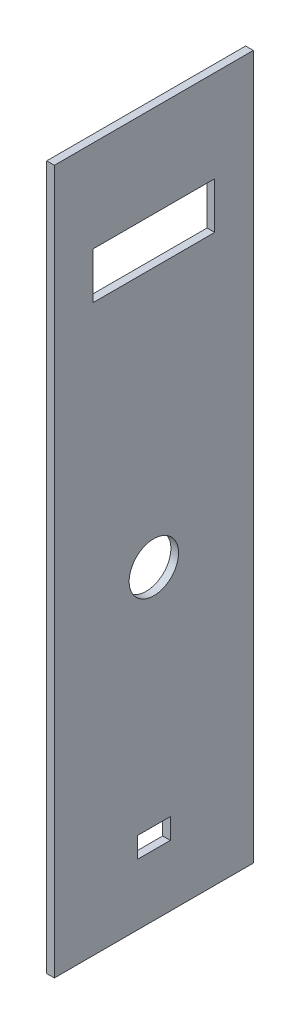
SolidWorks part; units mm, degrees
ref_plane "Front Plane" through (0, 0, 0) normal (0, 0, 1) x (1, 0, 0)
ref_plane "Top Plane" through (0, 0, 0) normal (0, 1, 0) x (1, 0, 0)
ref_plane "Right Plane" through (0, 0, 0) normal (1, 0, 0) x (0, 0, -1)
sketch "Sketch1" plane through (0, 0, 0) normal (1, 0, 0) x (0, 0, -1)
  line L1 (0, 0) -> (82.55, 0)
  line L2 (0, 0) -> (0, 292.1)
  line L3 (0, 292.1) -> (82.55, 292.1)
  line L4 (82.55, 0) -> (82.55, 292.1)
  dimension "D1" = 82.55
  dimension "D2" = 292.1
extrude "Boss-Extrude1" add sketch "Sketch1" along normal blind 3.175 contours L3 L4 L1 L2
sketch "Sketch2" plane through (0, 0, 0) normal (-1, 0, 0) x (0, 0, 1)
  line L0 (0, 292.1) -> (-82.55, 292.1) construction
  line L1 (-66.548, 234.696) -> (-16.002, 234.696)
  line L2 (-66.548, 234.696) -> (-66.548, 254)
  line L3 (-66.548, 254) -> (-16.002, 254)
  line L4 (-16.002, 234.696) -> (-16.002, 254)
  line L5 (0, 292.1) -> (-82.55, 292.1) construction
  point P8 (-41.275, 292.1)
  point P9 (-41.275, 254)
  dimension "D1" = 50.546
  dimension "D2" = 19.304
  dimension "D3" = 38.1
extrude "Cut-Extrude1" cut sketch "Sketch2" against normal up to next
ref_plane "Plane1" through (0, 0, -41.275) normal (0, 0, -1) x (-1, 0, 0)
sketch "Sketch4" plane through (0, 0, 0) normal (-1, 0, 0) x (0, 0, 1)
  line L0 (-41.275, 1.7463) -> (-41.275, -1.7462) construction
  line L2 (0, 0) -> (-82.55, 0) construction
  circle A0 centre (-41.275, 127) radius 10.25
  point P1 (0, 0)
  dimension "D1" = 20.5
  dimension "D2" = 127
extrude "Cut-Extrude2" cut sketch "Sketch4" against normal up to next
sketch "Sketch5" plane through (0, 0, 0) normal (-1, 0, 0) x (0, 0, 1)
  line L0 (-41.275, 1.7463) -> (-41.275, -1.7462) construction
  line L1 (-48.125, 33.95) -> (-34.425, 33.95)
  line L2 (-48.125, 33.95) -> (-48.125, 25.4)
  line L3 (-48.125, 25.4) -> (-34.425, 25.4)
  line L4 (-34.425, 33.95) -> (-34.425, 25.4)
  line L5 (0, 0) -> (-82.55, 0) construction
  point P4 (-41.275, 33.95)
  dimension "D1" = 8.55
  dimension "D2" = 13.7
  dimension "D3" = 25.4
extrude "Cut-Extrude3" cut sketch "Sketch5" against normal up to next
